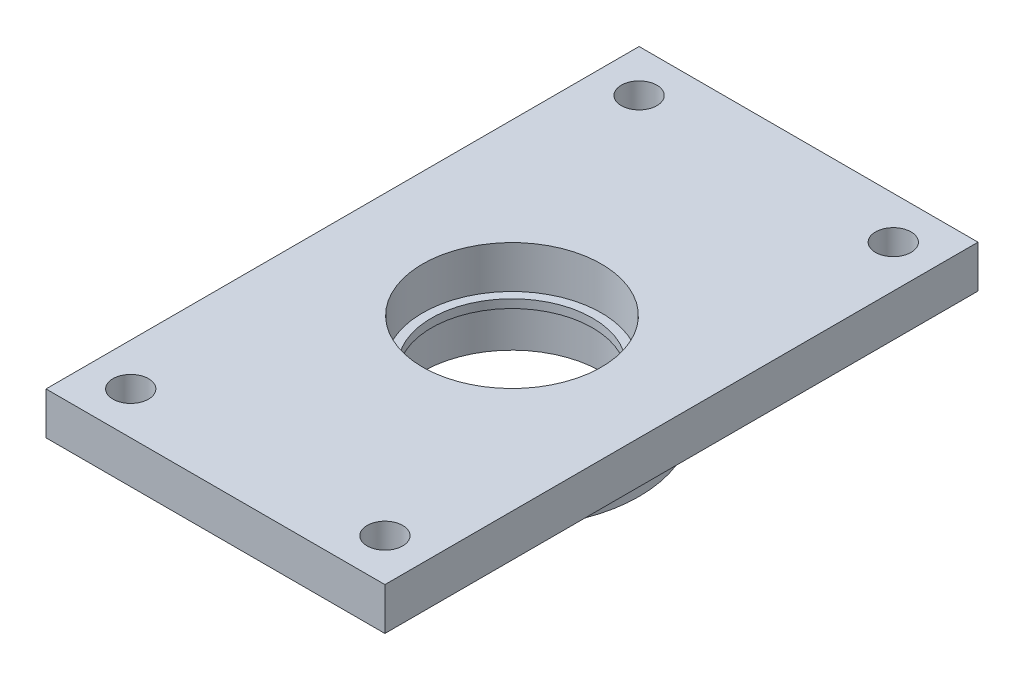
SolidWorks part; units mm, degrees
ref_plane "前视基准面" through (0, 0, 0) normal (0, 0, 1) x (1, 0, 0)
ref_plane "上视基准面" through (0, 0, 0) normal (0, 1, 0) x (1, 0, 0)
ref_plane "右视基准面" through (0, 0, 0) normal (1, 0, 0) x (0, 0, -1)
sketch "草图1" plane through (0, 0, 0) normal (0, 1, 0) x (1, 0, 0)
  line L0 (0, 0) -> (0, -58.7848) construction
  line L1 (-20, 35) -> (20, 35)
  line L2 (-20, 35) -> (-20, -35)
  line L3 (-20, -35) -> (20, -35)
  line L4 (20, 35) -> (20, -35)
  line L5 (-20, 35) -> (20, -35) construction
  line L6 (-20, -35) -> (20, 35) construction
  line L7 (0, 0) -> (35.3627, 0) construction
  line L8 (-15, -58.7848) -> (-15, 35) construction
  circle A0 centre (-15, -30) radius 2.1
  circle A1 centre (15, -30) radius 2.1
  circle A2 centre (15, 30) radius 2.1
  circle A3 centre (-15, 30) radius 2.1
  point P0 (0, 0)
  dimension "D5" = 4.2
  dimension "D1" = 70
  dimension "D2" = 40
  dimension "D3" = 5
  dimension "D4" = 5
  dimension "D6" = 60
  dimension "D7" = 30
extrude "凸台-拉伸1" add sketch "草图1" along normal blind 11
sketch "草图2" plane through (0, 11, 0) normal (0, 1, 0) x (1, 0, 0)
  circle A0 centre (0, 0) radius 9.5
  dimension "D1" = 19
extrude "切除-拉伸1" cut sketch "草图2" against normal blind 11
sketch "草图3" plane through (0, 11, 0) normal (0, 1, 0) x (1, 0, 0)
  circle A0 centre (0, 0) radius 10.55
  dimension "D1" = 21.1
extrude "切除-拉伸2" cut sketch "草图3" against normal blind 5
sketch "草图4" plane through (0, 0, 0) normal (0, -1, 0) x (1, 0, 0)
  circle A0 centre (0, 0) radius 10.55
  dimension "D1" = 21.1
extrude "切除-拉伸3" cut sketch "草图4" against normal blind 5
sketch "草图5" plane through (0, 0, 0) normal (0, -1, 0) x (1, 0, 0)
  line L0 (-20, 35) -> (20, 35) construction
  line L2 (20, -35) -> (-20, -35) construction
  line L4 (-20, 35) -> (20, 35)
  line L5 (20, 35) -> (20, -35)
  line L6 (20, -35) -> (-20, -35)
  line L7 (-20, -35) -> (-20, 35)
  circle A0 centre (0, 0) radius 15
  line M7 (20, -35) -> (20, 35)
  line M8 (20, 35) -> (-20, 35)
  line M9 (-20, 35) -> (-20, -35)
  line M10 (-20, -35) -> (20, -35)
  circle M11 centre (-15, 30) radius 2.1
  circle M12 centre (15, 30) radius 2.1
  circle M13 centre (15, -30) radius 2.1
  circle M14 centre (-15, -30) radius 2.1
  dimension "D1" = 30
extrude "切除-拉伸4" cut sketch "草图5" against normal up to surface (6 mm away) contours A0 L7 M10 M7 M14 M13 | A0 L5 M8 M9 M11 M12 region at (0, 0, 34.1938) up to face at (0, 6, 10.55)
